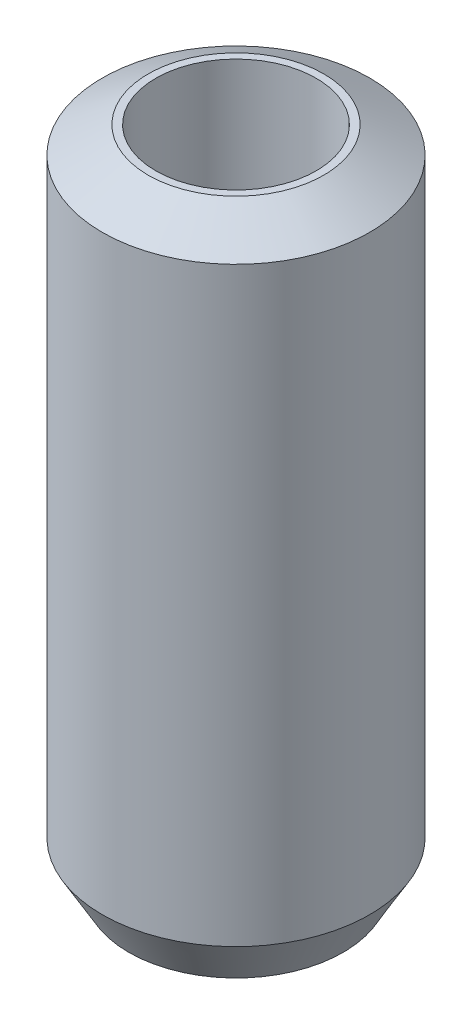
SolidWorks part; units mm, degrees
ref_plane "Front Plane" through (0, 0, 0) normal (0, 0, 1) x (1, 0, 0)
ref_plane "Top Plane" through (0, 0, 0) normal (0, 1, 0) x (1, 0, 0)
ref_plane "Right Plane" through (0, 0, 0) normal (1, 0, 0) x (0, 0, -1)
sketch "Sketch1" plane through (0, 0, 0) normal (0, 1, 0) x (1, 0, 0)
  circle A0 centre (0, 0) radius 12.5
  dimension "SHAFT_OD" = 25
extrude "Boss-Extrude1" add sketch "Sketch1" along normal blind 62.0073
sketch "Sketch2" plane through (0, 0, 0) normal (0, 1, 0) x (1, 0, 0)
  circle A0 centre (0, 0) radius 7.5004
  dimension "BORE_D" = 15.0008
extrude "Cut-Extrude1" cut sketch "Sketch2" along normal through all
chamfer "Chamfer1" distance 2.4787 angle 60 2 edges at (0, 62.0073, 12.5) (0, 0, 12.5) first distance on face at (0, 62.0073, 12.5) first distance on face at (0, 0, 7.5004)
